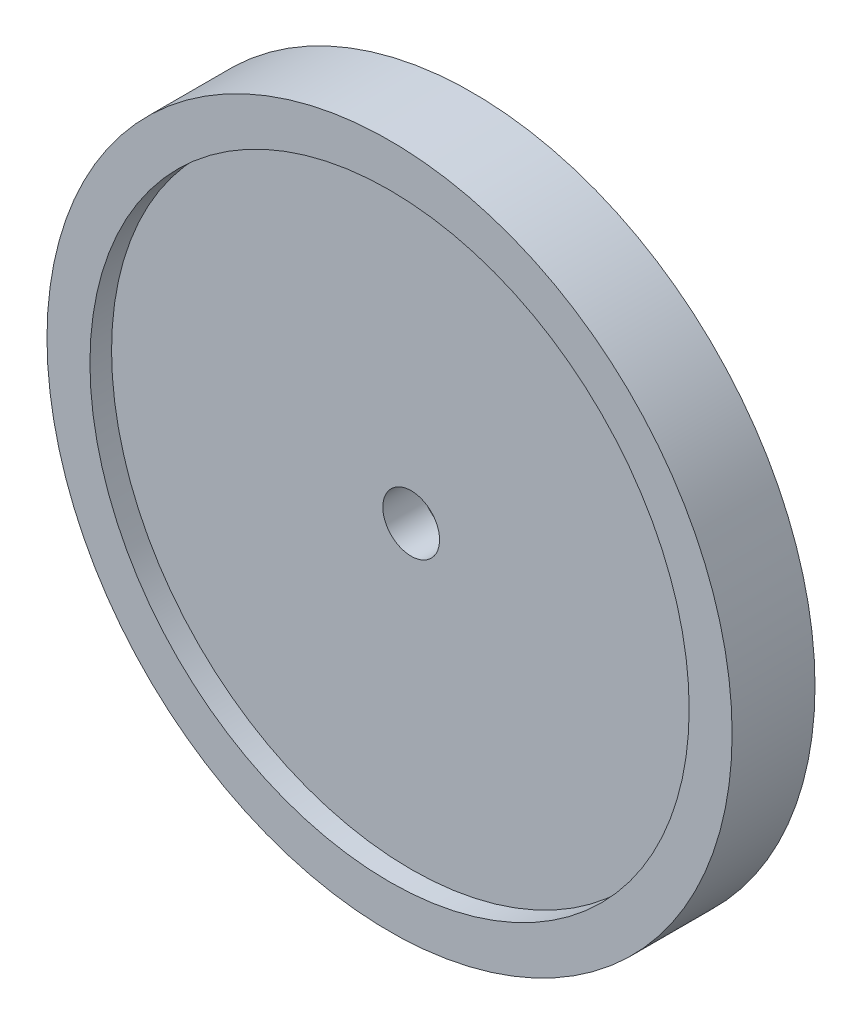
SolidWorks part; units mm, degrees
ref_plane "Front Plane" through (0, 0, 0) normal (0, 0, 1) x (1, 0, 0)
ref_plane "Top Plane" through (0, 0, 0) normal (0, 1, 0) x (1, 0, 0)
ref_plane "Right Plane" through (0, 0, 0) normal (1, 0, 0) x (0, 0, -1)
sketch "Sketch1" plane through (0, 0, 3.175) normal (0, 0, 1) x (1, 0, 0)
  circle A1 centre (-35.5331, 0) radius 24.145
  circle A2 centre (-35.5331, 0) radius 2
  circle A3 centre (-35.5331, 0) radius 24.145 construction
  dimension "D1" = 4
extrude "Boss-Extrude1" add sketch "Sketch1" along normal blind 5.842
sketch "Sketch2" plane through (0, 0, 9.017) normal (0, 0, 1) x (1, 0, 0)
  circle A0 centre (-35.5331, 0) radius 4.2545
  circle A1 centre (-35.5331, 0) radius 21.1176
  circle M4 centre (-35.5331, 0) radius 2
extrude "Cut-Extrude1" cut sketch "Sketch2" against normal blind 1.524 contours A1 A0 | A0 M4 | M4 region at (-39.6673, 0, 9.017) region at (-56.0535, 0, 9.017) region at (-35.5331, 0, 9.017)
ref_plane "Plane1" through (0, 0, 6.096) normal (0, 0, 1) x (1, 0, 0)
mirror "Mirror1" about plane through (0, 0, 6.096) normal (0, 0, 1) of "Cut-Extrude1"
